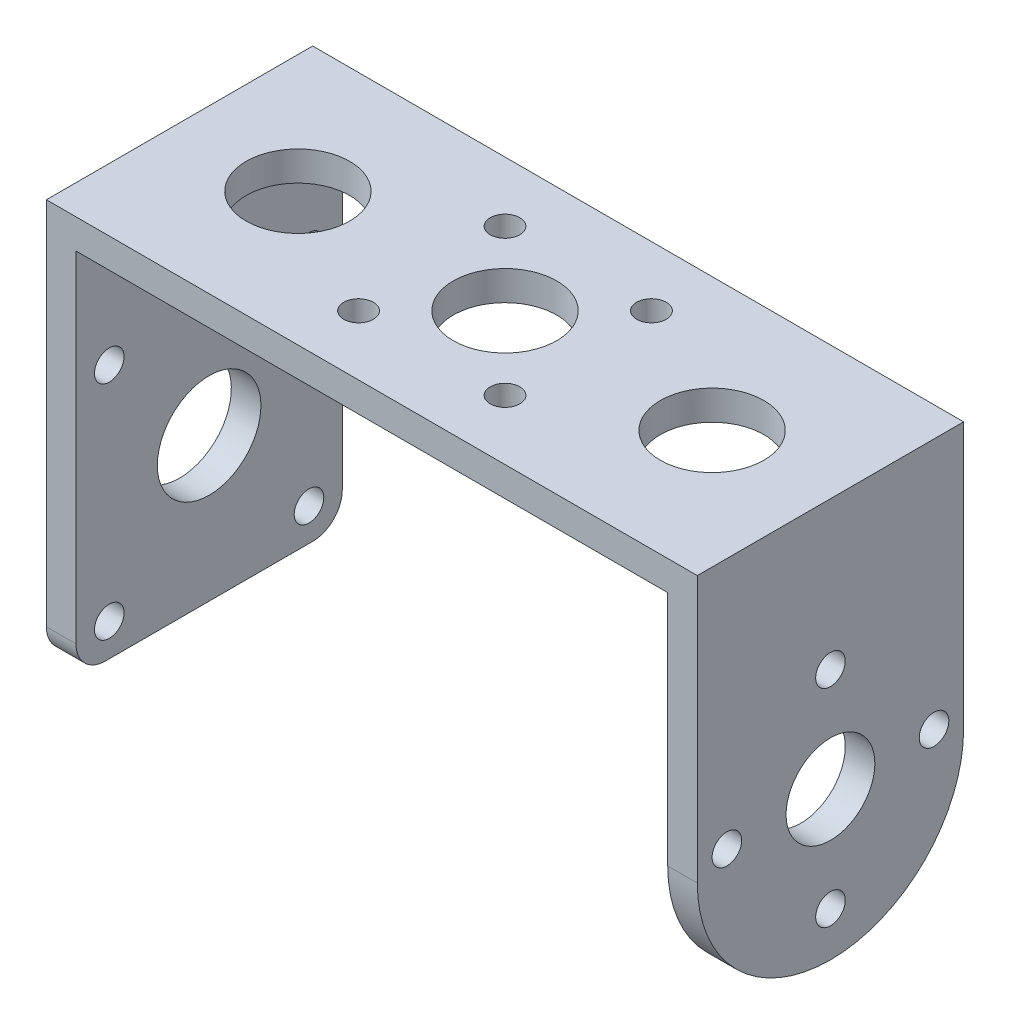
SolidWorks part; units mm, degrees
ref_plane "Front Plane" through (0, 0, 0) normal (0, 0, 1) x (1, 0, 0)
ref_plane "Top Plane" through (0, 0, 0) normal (0, 1, 0) x (1, 0, 0)
ref_plane "Right Plane" through (0, 0, 0) normal (1, 0, 0) x (0, 0, -1)
sketch "Sketch1" plane through (0, 0, 0) normal (0, 0, 1) x (1, 0, 0)
  line L0 (-22, -13.5) -> (-20, -13.5)
  line L1 (-22, 13.5) -> (22, 13.5)
  line L2 (-22, 13.5) -> (-22, -13.5)
  line L3 (-20, -13.5) -> (-20, 11.5)
  line L4 (22, 13.5) -> (22, -13.5)
  line L7 (-20, 11.5) -> (20, 11.5)
  line L8 (20, 11.5) -> (20, -13.5)
  line L9 (20, -13.5) -> (22, -13.5)
  point P0 (0, 0)
  dimension "D1" = 44
  dimension "D2" = 27
  dimension "D3" = 2
  dimension "D4" = 2
extrude "Boss-Extrude1" add sketch "Sketch1" along normal blind 18
fillet "Fillet1" radius 9 2 edges at (21, -13.5, 0) (21, -13.5, 18)
fillet "Fillet2" radius 2 2 edges at (-21, -13.5, 0) (-21, -13.5, 18)
sketch "Sketch2" plane through (22, 0, 0) normal (1, 0, 0) x (0, 0, -1)
  line L0 (-9, -13.5) -> (-9, 6.5) construction
  circle A0 centre (-9, -3.5) radius 3
  circle A1 centre (-9, -10.5) radius 1
  circle A2 centre (-16, -3.5) radius 1
  circle A3 centre (-9, 3.5) radius 1
  circle A4 centre (-2, -3.5) radius 1
  point P18 (-9, -3.5)
  dimension "D1" = 10
  dimension "D3" = 2
  dimension "D4" = 6
  dimension "D2" = 7
extrude "Cut-Extrude1" cut sketch "Sketch2" against normal up to next
sketch "Sketch3" plane through (-22, 0, 0) normal (-1, 0, 0) x (0, 0, 1)
  line L0 (9, -13.5) -> (9, 13.5) construction
  line L1 (16, -13.5) -> (2, -13.5) construction
  line L2 (18, 13.5) -> (0, 13.5) construction
  line L4 (2.25, 3.7) -> (15.75, 3.7)
  line L5 (2.25, 3.7) -> (2.25, -11.3)
  line L6 (2.25, -11.3) -> (15.75, -11.3)
  line L7 (15.75, 3.7) -> (15.75, -11.3)
  line L8 (2.25, 3.7) -> (15.75, -11.3) construction
  line L9 (2.25, -11.3) -> (15.75, 3.7) construction
  circle A0 centre (9, -3.8) radius 3.5
  circle A1 centre (15.75, 3.7) radius 1
  circle A2 centre (2.25, 3.7) radius 1
  circle A3 centre (2.25, -11.3) radius 1
  circle A4 centre (15.75, -11.3) radius 1
  dimension "D1" = 13.5
  dimension "D4" = 2
  dimension "D5" = 7
  dimension "D2" = 9.7
  dimension "D3" = 15
  dimension "D6" = 2
extrude "Cut-Extrude2" cut sketch "Sketch3" against normal up to next contours A0 | L4 A2 L5 | L5 A2 L4 | L7 A1 L4 | L4 A1 L7 | L6 A4 L7 | L7 A4 L6 | L6 A3 L5 | L5 A3 L6 region at (-22, 3.8415, 2.1085) region at (-22, 3.2756, 2.6744) region at (-22, 3.8415, 15.8915) region at (-22, 3.2756, 15.3256) region at (-22, -10.8756, 2.6744) region at (-22, -11.4415, 2.1085) region at (-22, -11.4415, 15.8915) region at (-22, -10.8756, 15.3256) region at (-22, -3.8, 9)
sketch "Sketch4" plane through (0, 13.5, 0) normal (0, 1, 0) x (1, 0, 0)
  line L0 (0, 0) -> (0, -18) construction
  line L1 (22, -18) -> (-22, -18) construction
  line L3 (-4.9497, -4.0503) -> (4.9497, -4.0503)
  line L4 (-4.9497, -4.0503) -> (-4.9497, -13.9497)
  line L5 (-4.9497, -13.9497) -> (4.9497, -13.9497)
  line L6 (4.9497, -4.0503) -> (4.9497, -13.9497)
  line L7 (-4.9497, -4.0503) -> (4.9497, -13.9497) construction
  line L8 (-4.9497, -13.9497) -> (4.9497, -4.0503) construction
  circle A0 centre (0, -9) radius 3.5
  circle A1 centre (4.9497, -4.0503) radius 1
  circle A2 centre (4.9497, -13.9497) radius 1
  circle A3 centre (-4.9497, -13.9497) radius 1
  circle A4 centre (-4.9497, -4.0503) radius 1
  point P5 (0, -9)
  point P22 (0, -9)
  dimension "D1" = 7
  dimension "D3" = 2
  dimension "D2" = 7
extrude "Cut-Extrude3" cut sketch "Sketch4" against normal blind 20 contours L6 A1 L3 | L3 A1 L6 | A0 | L3 A4 L4 | L4 A4 L3 | L4 A3 L5 | L5 A3 L4 | L6 A2 L5 | L5 A2 L6 | A3 region at (-5.0912, 13.5, 3.9088) region at (-4.5253, 13.5, 4.4747) region at (5.0912, 13.5, 3.9088) region at (4.5253, 13.5, 4.4747) region at (-4.5253, 13.5, 13.5253) region at (-5.0912, 13.5, 14.0912) region at (5.0912, 13.5, 14.0912) region at (4.5253, 13.5, 13.5253) region at (0, 13.5, 9)
sketch "Sketch5" plane through (0, 13.5, 0) normal (0, 1, 0) x (1, 0, 0)
  line L0 (-22, -9) -> (22, -9) construction
  line L1 (-22, -18) -> (-22, 0) construction
  line L2 (22, -18) -> (22, 0) construction
  line L3 (0, 0) -> (0, -18) construction
  line L4 (22, 0) -> (-22, 0) construction
  line L5 (22, -18) -> (-22, -18) construction
  circle A0 centre (-14, -9) radius 3.5
  circle A1 centre (14, -9) radius 3.5
  dimension "D1" = 14
  dimension "D2" = 7
extrude "Cut-Extrude4" cut sketch "Sketch5" against normal up to next
